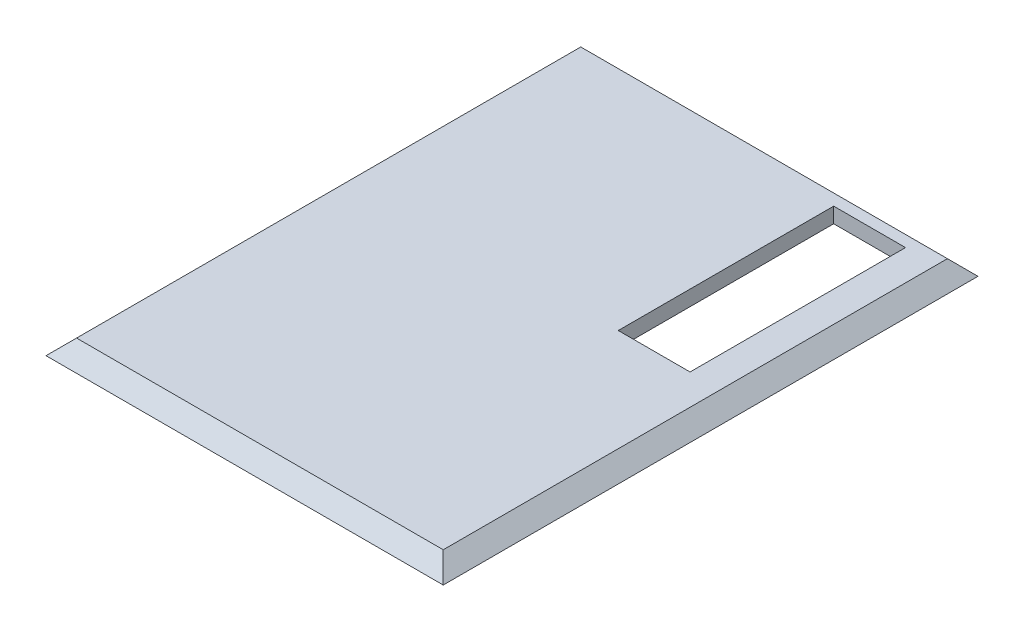
SolidWorks part; units mm, degrees
ref_plane "Front Plane" through (0, 0, 0) normal (0, 0, 1) x (1, 0, 0)
ref_plane "Top Plane" through (0, 0, 0) normal (0, 1, 0) x (1, 0, 0)
ref_plane "Right Plane" through (0, 0, 0) normal (1, 0, 0) x (0, 0, -1)
sketch "Sketch1" plane through (0, 0, 0) normal (0, 1, 0) x (1, 0, 0)
  line L1 (-65, -87.5) -> (65, -87.5)
  line L2 (-65, -87.5) -> (-65, 87.5)
  line L3 (-65, 87.5) -> (65, 87.5)
  line L4 (65, -87.5) -> (65, 87.5)
  line L5 (-65, -87.5) -> (65, 87.5) construction
  line L6 (-65, 87.5) -> (65, -87.5) construction
  point P0 (0, 0)
extrude "Boss-Extrude1" add sketch "Sketch1" along normal blind 5
chamfer "Chamfer1" distance 5 angle 45 4 edges at (65, 5, 0) (0, 5, -87.5) (-65, 5, 0) (0, 5, 87.5)
sketch "Sketch2" plane through (0, 0, 0) normal (0, -1, 0) x (1, 0, 0)
  line L0 (0, 0) -> (-1.5, 0)
  line L1 (5.5, 0) -> (-5.5, 0) construction
  line L2 (0, 0) -> (0, 5)
  line L3 (0, -5.5) -> (0, 5.5) construction
  line L5 (1.5, -5) -> (-1.5, -5)
  line L6 (1.5, -5) -> (1.5, 5)
  line L7 (1.5, 5) -> (-1.5, 5)
  line L8 (-1.5, -5) -> (-1.5, 5)
  line L9 (1.5, -5) -> (-1.5, 5) construction
  line L10 (1.5, 5) -> (-1.5, -5) construction
extrude "Boss-Extrude2" add sketch "Sketch2" along normal blind 5 contours L8 L5 L6 L7 L2 L0 | L8 L0 L2 L7 region at (0.25, 0, -0.8333) region at (-0.75, 0, 2.5)
fillet "Fillet2" radius 1 4 edges at (1.5, -5, 0) (0, -5, -5) (-1.5, -5, 0) (0, -5, 5)
fillet "Fillet3" radius 1 8 edges at (1.2071, -4.7071, -4.7071) (-1.2071, -4.7071, -4.7071) (-1.2071, -4.7071, 4.7071) (1.2071, -4.7071, 4.7071) (1.5, -2, -5) (-1.5, -2, -5) (-1.5, -2, 5) (1.5, -2, 5)
sketch "Sketch4" plane through (0, 0, 0) normal (0, -1, 0) x (1, 0, 0)
  line L0 (0, 0) -> (65, 0)
  line L1 (65, 87.5) -> (65, -87.5) construction
  line L2 (65, 0) -> (65, -87.5)
  line L3 (50, -43.75) -> (50, -8.275)
  line L4 (26.5, -8.275) -> (26.5, -78.775)
  line L6 (50, -8.275) -> (26.5, -8.275)
  line L8 (50, -43.75) -> (50, -78.775)
  line L9 (50, -78.775) -> (26.5, -78.775)
extrude "Cut-Extrude1" cut sketch "Sketch4" against normal blind 5 contours L9 L8 L3 L6 L4 region at (38.25, 0, -43.525)
